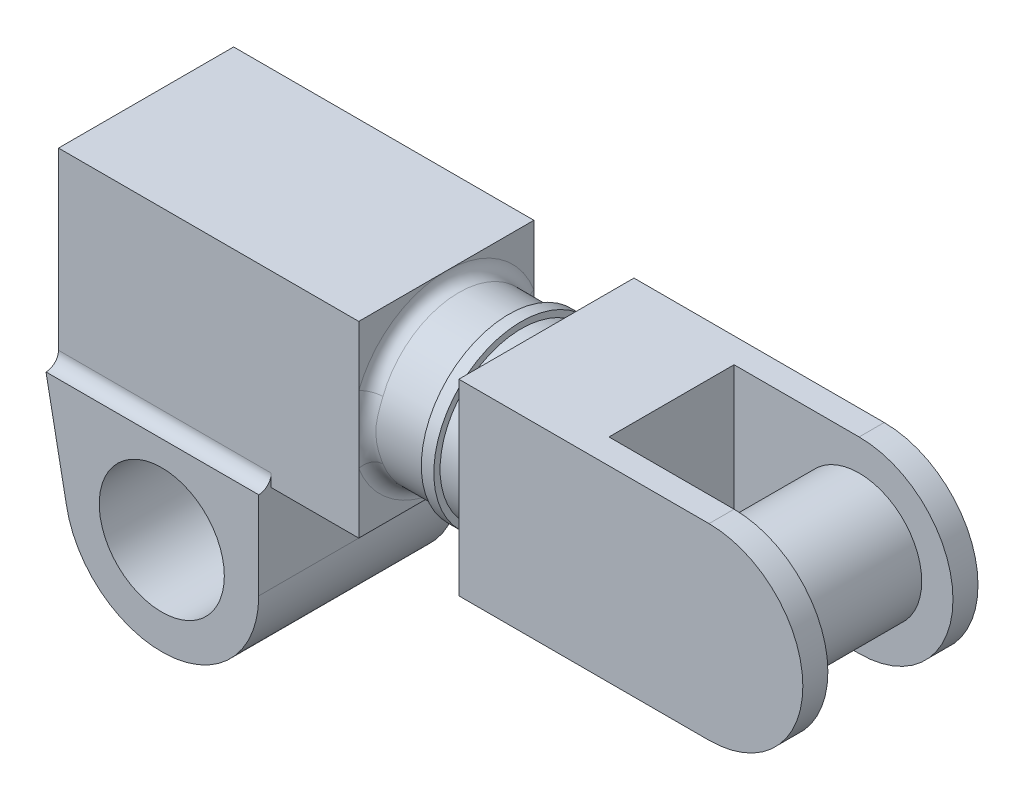
SolidWorks part; units mm, degrees
ref_plane "Front Plane" through (0, 0, 0) normal (0, 0, 1) x (1, 0, 0)
ref_plane "Top Plane" through (0, 0, 0) normal (0, 1, 0) x (1, 0, 0)
ref_plane "Right Plane" through (0, 0, 0) normal (1, 0, 0) x (0, 0, -1)
sketch "Sketch1" plane through (0, 0, 0) normal (1, 0, 0) x (0, 0, -1)
  line L1 (-70, 75) -> (70, 75)
  line L2 (-70, 75) -> (-70, -75)
  line L3 (-70, -75) -> (70, -75)
  line L4 (70, 75) -> (70, -75)
  line L5 (-70, 75) -> (70, -75) construction
  line L6 (-70, -75) -> (70, 75) construction
  point P0 (0, 0)
  dimension "D1" = 140
  dimension "D2" = 150
extrude "Boss-Extrude1" add sketch "Sketch1" along normal blind 240
sketch "Sketch2" plane through (240, 0, 0) normal (1, 0, 0) x (0, 0, -1)
  circle A0 centre (0, 0) radius 65
  dimension "D1" = 130
extrude "Boss-Extrude2" add sketch "Sketch2" along normal blind 50
sketch "Sketch3" plane through (290, 0, 0) normal (1, 0, 0) x (0, 0, -1)
  circle A0 centre (0, 0) radius 70
  dimension "D1" = 140
extrude "Boss-Extrude4" add sketch "Sketch3" along normal blind 10
sketch "Sketch5" plane through (0, 0, 0) normal (0, 0, 1) x (1, 0, 0)
  line L0 (0, -75) -> (16.2188, -158.4383)
  line L1 (0, 75) -> (0, -75) construction
  line L2 (170.0448, -145) -> (170.0448, -75)
  line L3 (240, -75) -> (0, -75) construction
  line L4 (0, -75) -> (170.0448, -75)
  circle A0 centre (92.5448, -145) radius 50
  arc A1 (16.2188, -158.4383) -> (170.0448, -145) centre (92.5448, -145) ccw
  dimension "D1" = 155
  dimension "D2" = 100
  dimension "D3" = 191
  dimension "D4" = 85
  dimension "D5" = 70
extrude "Boss-Extrude5" add sketch "Sketch5" along normal mid plane 160
fillet "Fillet1" radius 10 3 edges at (85.0224, -75, -70) (240, 0, -65) (85.0224, -75, 70)
sketch "Sketch6" plane through (300, 0, 0) normal (1, 0, 0) x (0, 0, -1)
  circle A0 centre (0, 0) radius 65
  dimension "D1" = 130
extrude "Boss-Extrude6" add sketch "Sketch6" along normal blind 20
sketch "Sketch7" plane through (0, 0, 0) normal (0, 0, 1) x (1, 0, 0)
  line L0 (520, 75) -> (320, 75)
  line L1 (320, 75) -> (320, -75)
  line L2 (320, -75) -> (520, -75)
  line L3 (320, -65) -> (320, 65) construction
  arc A0 (520, -75) -> (520, 75) centre (520, 0) ccw
  dimension "D1" = 150
  dimension "D2" = 200
extrude "Boss-Extrude8" add sketch "Sketch7" along normal mid plane 140
sketch "Sketch8" plane through (0, 0, 0) normal (0, 0, 1) x (1, 0, 0)
  line L0 (520, 75) -> (420, 75)
  line L1 (520, 75) -> (320, 75) construction
  line L2 (420, 75) -> (420, -75)
  line L3 (320, -75) -> (520, -75) construction
  line L4 (420, -75) -> (520, -75)
  arc A0 (520, -75) -> (520, 75) centre (520, 0) ccw construction
  arc A1 (520, -75) -> (520, 75) centre (520, 0) ccw
extrude "Cut-Extrude1" cut sketch "Sketch8" against normal mid plane 100
sketch "Sketch9" plane through (0, 0, 50) normal (0, 0, -1) x (-1, 0, 0)
  circle A0 centre (-520, 0) radius 50
  dimension "D1" = 100
extrude "Boss-Extrude9" add sketch "Sketch9" along normal blind 100
